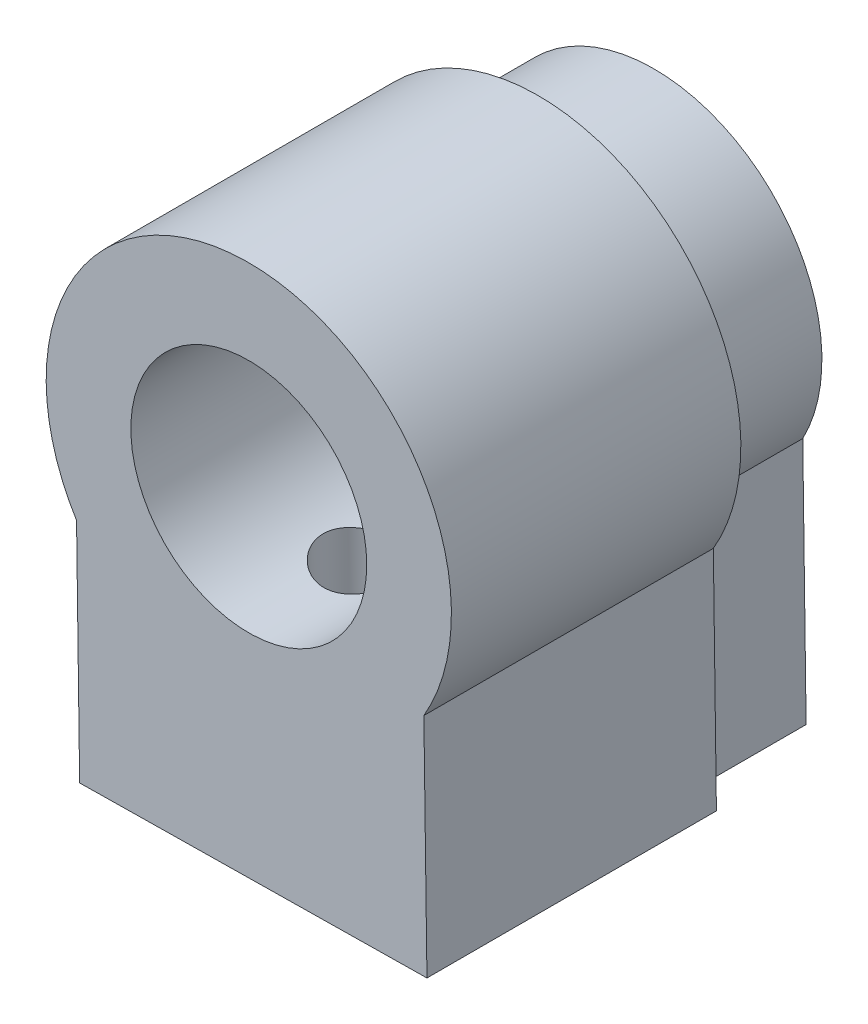
SolidWorks part; units mm, degrees
ref_plane "Front Plane" through (0, 0, 0) normal (0, 0, 1) x (1, 0, 0)
ref_plane "Top Plane" through (0, 0, 0) normal (0, 1, 0) x (1, 0, 0)
ref_plane "Right Plane" through (0, 0, 0) normal (1, 0, 0) x (0, 0, -1)
sketch "Sketch1" plane through (0, 0, 0) normal (0, 0, 1) x (1, 0, 0)
  line L0 (-5.1495, -4.7726) -> (5.0505, -4.6333)
  line L1 (-5.1495, -4.7726) -> (-5.0335, -13.2726)
  line L2 (5.0505, -4.6333) -> (5.1665, -13.1333)
  line L3 (-5.0335, -13.2726) -> (5.1665, -13.1333)
  circle A0 centre (-0.0873, -1.9418) radius 5.8
  dimension "D1" = 11.6
  dimension "D2" = 5.8
  dimension "D3" = 5.8
  dimension "D4" = 10.2
  dimension "D5" = 8.5
extrude "Boss-Extrude1" add sketch "Sketch1" along normal blind 4 contours A0 L1 L3 L2 | L0 A0 | L0 A0 region at (-0.1017, -0.884, 0) region at (0.0225, -9.9776, 0) region at (-0.0325, -5.9505, 0)
sketch "Sketch2" plane through (0, 0, 4) normal (0, 0, 1) x (1, 0, 0)
  line L0 (5.9614, -5.4651) -> (-6.0375, -5.629)
  line L1 (5.9614, -5.4651) -> (6.068, -13.2651)
  line L2 (-6.0375, -5.629) -> (-5.9309, -13.429)
  line L3 (6.068, -13.2651) -> (-5.9309, -13.429)
  line L4 (-5.0335, -13.2726) -> (5.1665, -13.1333) construction
  circle A0 centre (-0.0873, -1.9418) radius 7
  arc A1 (5.0505, -4.6333) -> (-5.1495, -4.7726) centre (-0.0873, -1.9418) ccw construction
  circle A2 centre (-0.0873, -1.9418) radius 4.075
  line M1 (5.1665, -13.1333) -> (5.0505, -4.6333)
  arc M2 (5.0505, -4.6333) -> (-5.1495, -4.7726) centre (-0.0873, -1.9418) ccw
  line M3 (-5.1495, -4.7726) -> (-5.0335, -13.2726)
  line M4 (-5.0335, -13.2726) -> (5.1665, -13.1333)
  dimension "D1" = 0
  dimension "D2" = 14
  dimension "D3" = 0
  dimension "D4" = 8.15
  dimension "D5" = 7
  dimension "D6" = 7
  dimension "D7" = 12
  dimension "D8" = 180
  dimension "D9" = 7.8
extrude "Boss-Extrude3" add sketch "Sketch2" along normal blind 10 contours L0 A0 M3 M2 M1 | A2 L0 M1 M2 M3 | A2 L0 A0 M3 M1 | A0 M3 M4 M1 | A0 L2 L3 L1 M1 M4 M3 | A0 L0 M1 | L0 A0 M3 region at (5.3786, -5.8837, 4) region at (5.5093, -5.2951, 4) region at (5.8698, -9.3671, 4) region at (-0.0177, -7.0347, 4) region at (3.4593, -5.3495, 4) region at (0.0322, -10.6902, 4) region at (-5.4434, -6.0315, 4)
sketch "Sketch6" plane through (0.1823, -13.3455, 0) normal (0.0137, -0.9999, 0) x (-0.9999, -0.0137, 0)
  line L0 (-5.8862, -14) -> (6.1138, -14) construction
  circle A0 centre (0.2412, -10) radius 1.35
  point P2 (0.1138, -14)
  dimension "D2" = 2.7
  dimension "D1" = 4
extrude "Cut-Extrude3" cut sketch "Sketch6" against normal blind 8.5
